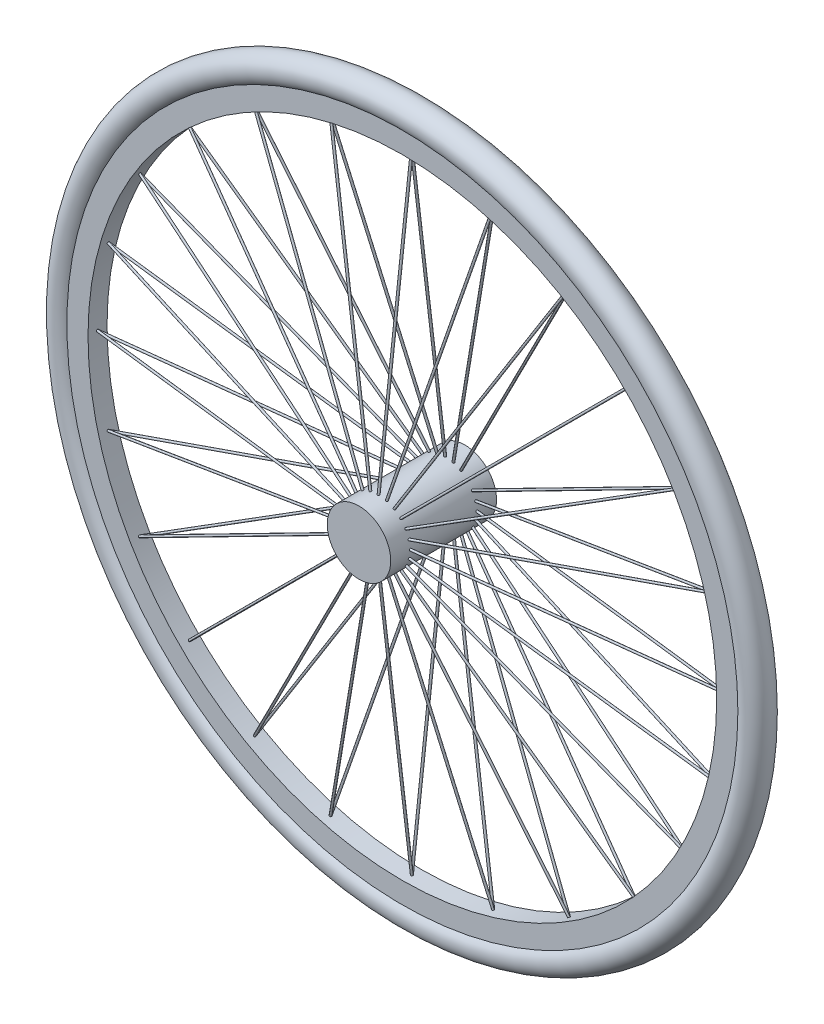
SolidWorks part; units mm, degrees
material "车轮"
ref_plane "前视基准面" through (0, 0, 0) normal (0, 0, 1) x (1, 0, 0)
ref_plane "上视基准面" through (0, 0, 0) normal (0, 1, 0) x (1, 0, 0)
ref_plane "右视基准面" through (0, 0, 0) normal (1, 0, 0) x (0, 0, -1)
other "Configuration Table"
sketch "草图1" plane through (0, 0, 0) normal (0, 0, 1) x (1, 0, 0)
  circle A0 centre (0, 0) radius 30
  dimension "D1" = 60
extrude "凸台-拉伸1" add sketch "草图1" along normal mid plane 100
sketch "草图2" plane through (0, 0, 0) normal (0, 1, 0) x (1, 0, 0)
  line L1 (297.1439, 9) -> (317.1439, 9)
  line L2 (297.1439, 9) -> (297.1439, -9)
  line L3 (297.1439, -9) -> (317.1439, -9)
  line L5 (297.1439, 9) -> (317.1439, -9) construction
  line L6 (297.1439, -9) -> (317.1439, 9) construction
  arc A0 (317.1439, -9) -> (317.1439, 9) centre (326.8, 0) ccw
  point P0 (307.1439, 0)
  dimension "D1" = 26.4
  dimension "D4" = 326.8
  dimension "D2" = 18
  dimension "D3" = 20
sketch "草图3" plane through (0, 0, 0) normal (0, 1, 0) x (1, 0, 0)
  line L0 (0, -50) -> (0, 50)
  line L1 (-30, -50) -> (30, -50) construction
  line L2 (30, 50) -> (-30, 50) construction
revolve "旋转1" add sketch "草图2" angle 360 about L0
sketch "草图5" plane through (0, 0, 0) normal (0, 1, 0) x (1, 0, 0)
  line L0 (297.1439, 9) -> (-297.1439, 9) construction
  line L3 (297.1439, 9) -> (-297.1439, 9)
  line L4 (0, -35) -> (297.1439, 0)
  line L5 (297.1439, -9) -> (297.1439, 9) construction
  arc A0 (326.8, -13.2) -> (326.8, 13.2) centre (326.8, 0) ccw construction
  arc A1 (326.8, -13.2) -> (326.8, 13.2) centre (326.8, 0) ccw
  dimension "D2" = 35
ref_plane "基准面1" through (0, 0, 35) normal (0.9931, 0, -0.117) x (-0.117, 0, -0.9931)
sketch "草图6" plane through (0, 0, 35) normal (0.9931, 0, -0.117) x (-0.117, 0, -0.9931)
  circle A0 centre (0, 0) radius 1
  dimension "D1" = 2
extrude "凸台-拉伸2" add sketch "草图6" along normal up to surface (299.3159 mm away) up to face at (297.1439, 0, 9)
pattern_circular "阵列(圆周)1" count 24 over 360 about axis through (0, 0, 50) along (0, 0, 1) of "凸台-拉伸2"
mirror "镜向1" about plane through (0, 0, 0) normal (0, 0, 1) of "阵列(圆周)1"
